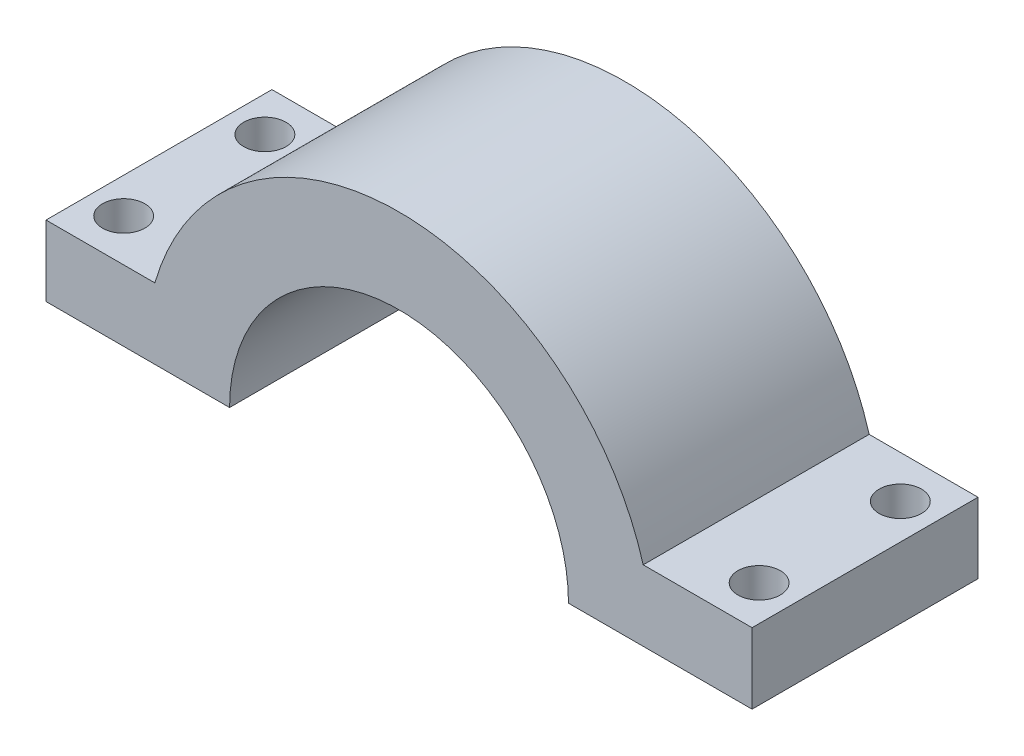
SolidWorks part; units mm, degrees
ref_plane "Front Plane" through (0, 0, 0) normal (0, 0, 1) x (1, 0, 0)
ref_plane "Top Plane" through (0, 0, 0) normal (0, 1, 0) x (1, 0, 0)
ref_plane "Right Plane" through (0, 0, 0) normal (1, 0, 0) x (0, 0, -1)
sketch "Sketch7" plane through (0, 0, 0) normal (0, 0, 1) x (1, 0, 0)
  line L17 (28.8688, -27.166) -> (28.8688, -22.166)
  line L20 (-21.1312, -22.166) -> (-21.1312, -27.166)
  line L24 (-21.1312, -27.166) -> (-8.1312, -27.166)
  line L25 (15.8688, -27.166) -> (28.8688, -27.166)
  line L28 (-13.4228, -22.166) -> (-21.1312, -22.166)
  line L29 (21.1604, -22.166) -> (28.8688, -22.166)
  line L30 (-21.1312, -27.166) -> (-8.1312, -27.166) construction
  arc A5 (-8.1312, -27.166) -> (15.8688, -27.166) centre (3.8688, -27.166) cw
  arc A6 (21.1604, -22.166) -> (-13.4228, -22.166) centre (3.8688, -27.166) ccw
  dimension "D3" = 13
  dimension "D4" = 50
  dimension "D2" = 12
  dimension "D1" = 13
  dimension "D7" = 5
  dimension "D8" = 5
extrude "Boss-Extrude1" add sketch "Sketch7" along normal blind 16
sketch "Sketch13" plane through (0, -22.166, 0) normal (0, 1, 0) x (1, 0, 0)
  line L42 (-13.4228, 0) -> (-21.1312, 0) construction
  line L43 (-21.1312, 0) -> (-13.4228, 0)
  line L44 (-21.1312, 0) -> (-21.1312, -16)
  line L45 (-21.1312, -16) -> (-13.4228, -16)
  line L46 (-13.4228, 0) -> (-13.4228, -16)
  line L48 (21.1604, 0) -> (28.8688, 0)
  line L49 (21.1604, 0) -> (21.1604, -16)
  line L50 (21.1604, -16) -> (28.8688, -16)
  line L51 (28.8688, 0) -> (28.8688, -16)
sketch "Sketch14" plane through (0, -27.166, 0) normal (0, 1, 0) x (1, 0, 0)
  line L8 (28.8688, -16) -> (28.8688, 0) construction
  line L9 (15.8688, -16) -> (28.8688, -16) construction
  line L10 (15.8688, 0) -> (28.8688, 0) construction
  line L11 (-21.1312, 0) -> (-8.1312, 0) construction
  line L12 (-21.1312, -16) -> (-21.1312, 0) construction
  line L14 (-21.1312, -16) -> (-8.1312, -16) construction
  circle A0 centre (-18.6312, -3) radius 1.5
  circle A1 centre (-18.6312, -13) radius 1.5
  circle A2 centre (26.3688, -3) radius 1.5
  circle A3 centre (26.3688, -13) radius 1.5
  dimension "D1" = 2.5
  dimension "D2" = 3
  dimension "D3" = 3
  dimension "D4" = 2.5
  dimension "D5" = 3
  dimension "D6" = 2.5
  dimension "D7" = 2.5
  dimension "D8" = 3
extrude "Cut-Extrude13" cut sketch "Sketch14" along normal blind 50
